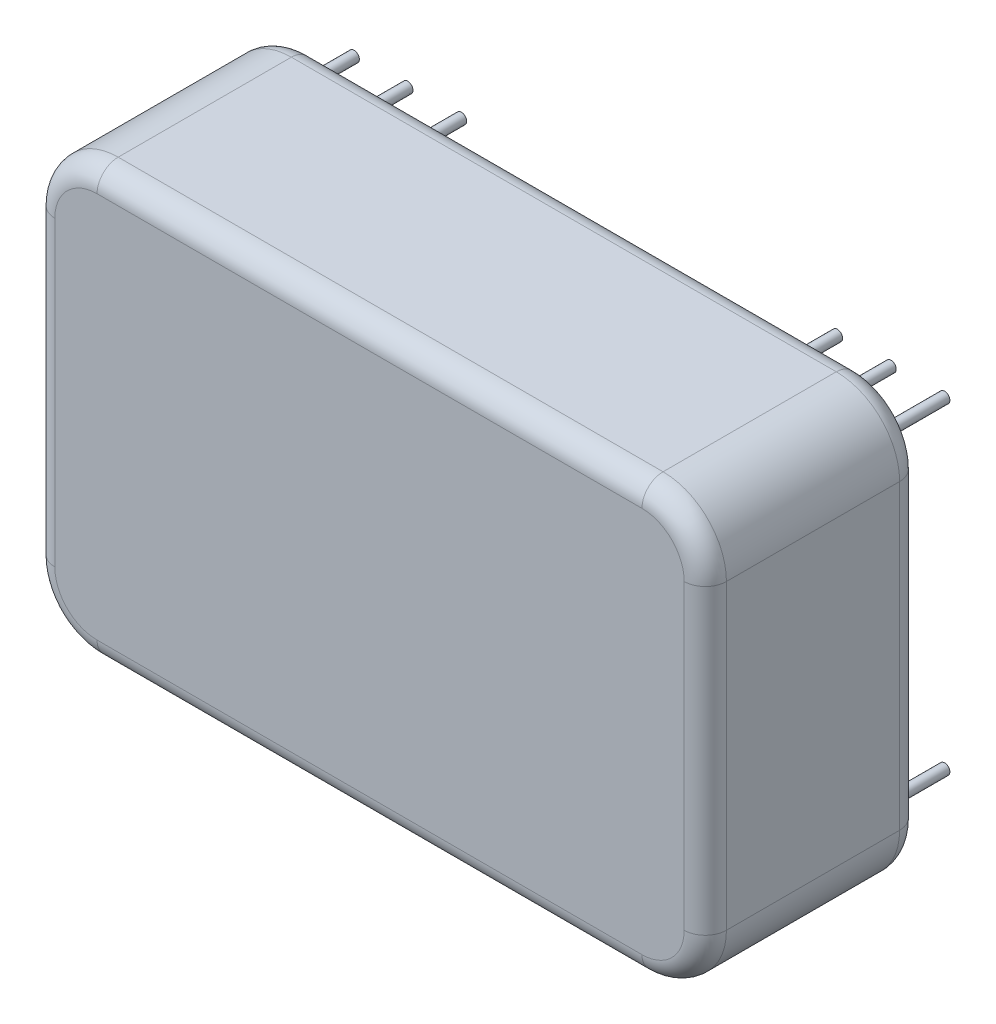
SolidWorks part; units mm, degrees
ref_plane "Спереди" through (0, 0, 0) normal (0, 0, 1) x (1, 0, 0)
ref_plane "Сверху" through (0, 0, 0) normal (0, 1, 0) x (1, 0, 0)
ref_plane "Справа" through (0, 0, 0) normal (1, 0, 0) x (0, 0, -1)
sketch "Эскиз1" plane through (0, 0, 0) normal (0, 0, 1) x (1, 0, 0)
  line L1 (-15.9, -10.15) -> (15.9, -10.15)
  line L2 (-15.9, -10.15) -> (-15.9, 10.15)
  line L3 (-15.9, 10.15) -> (15.9, 10.15)
  line L4 (15.9, -10.15) -> (15.9, 10.15)
  line L5 (-15.9, -10.15) -> (15.9, 10.15) construction
  line L6 (-15.9, 10.15) -> (15.9, -10.15) construction
  point P0 (0, 0)
  dimension "D1" = 31.8
  dimension "D2" = 20.3
extrude "Бобышка-Вытянуть1" add sketch "Эскиз1" along normal blind 10.2
fillet "Скругление2" radius 1 8 edges at (0, 10.15, 0) (15.9, 0, 0) (0, -10.15, 0) (-15.9, 0, 0) (0, 10.15, 10.2) (15.9, 0, 10.2) (0, -10.15, 10.2) (-15.9, 0, 10.2)
fillet "Скругление1" radius 3 12 edges at (-15.9, -10.15, 5.1) (15.9, -10.15, 5.1) (15.9, 10.15, 5.1) (-15.9, 10.15, 5.1) (-15.6071, 9.8571, 0.2929) (-15.6071, 9.8571, 9.9071) (15.6071, 9.8571, 0.2929) (15.6071, 9.8571, 9.9071) (15.6071, -9.8571, 0.2929) (15.6071, -9.8571, 9.9071) (-15.6071, -9.8571, 0.2929) (-15.6071, -9.8571, 9.9071)
sketch "Эскиз2" plane through (0, 0, 0) normal (0, 0, -1) x (-1, 0, 0)
  circle A0 centre (13.98, 7.62) radius 0.25
  circle A1 centre (8.9, 7.62) radius 0.25
  circle A2 centre (-11.44, 7.62) radius 0.25
  circle A3 centre (-13.98, 7.62) radius 0.25
  circle A4 centre (-13.98, -7.62) radius 0.25
  circle A5 centre (-11.44, -7.62) radius 0.25
  circle A6 centre (8.9, -7.62) radius 0.25
  circle A7 centre (13.98, -7.62) radius 0.25
  circle A8 centre (-8.9, 7.62) radius 0.25
  circle A9 centre (-8.9, -7.62) radius 0.25
  circle A10 centre (11.44, 7.62) radius 0.25
  circle A11 centre (11.44, -7.62) radius 0.25
  point P25 (0, 0)
  point P26 (0, 0)
  point P27 (0, 0)
  point P28 (0, 0)
  point P29 (11.557, -7.62)
  dimension "D1" = 0.5
  dimension "D2" = 7.62
  dimension "D3" = 7.62
  dimension "D4" = 5.08
  dimension "D5" = 2.54
  dimension "D6" = 27.96
  dimension "D7" = 13.98
  dimension "D8" = 2.54
  dimension "D9" = 2.54
extrude "Бобышка-Вытянуть2" add sketch "Эскиз2" along normal blind 3.05
